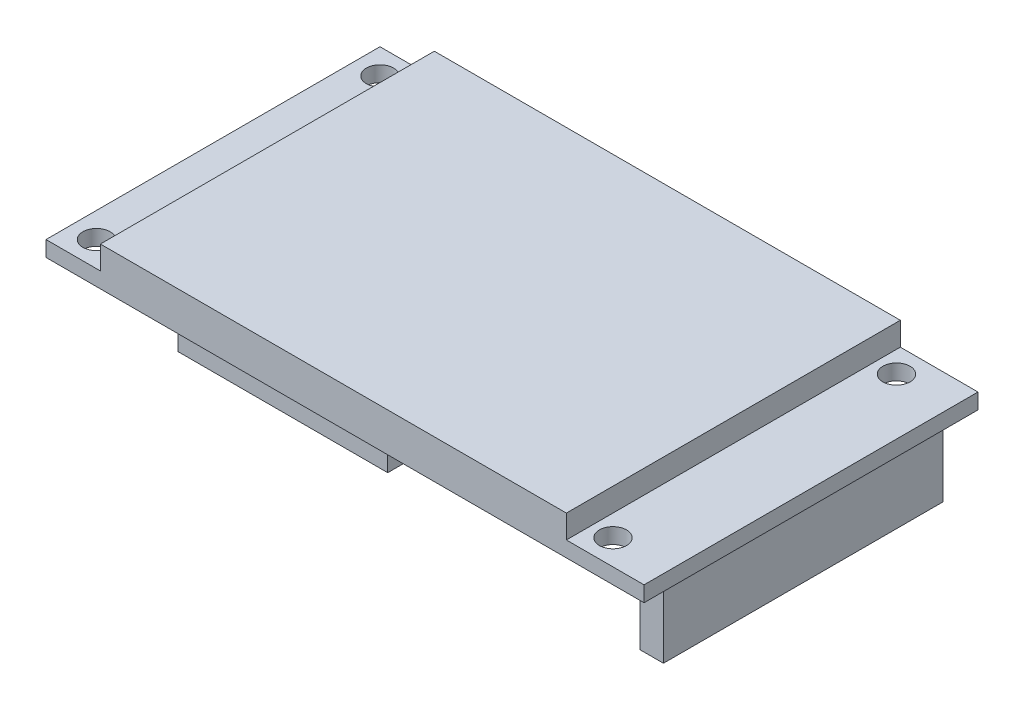
SolidWorks part; units mm, degrees
ref_plane "Front Plane" through (0, 0, 0) normal (0, 0, 1) x (1, 0, 0)
ref_plane "Top Plane" through (0, 0, 0) normal (0, 1, 0) x (1, 0, 0)
ref_plane "Right Plane" through (0, 0, 0) normal (1, 0, 0) x (0, 0, -1)
sketch "Sketch1" plane through (0, 0, 0) normal (0, 1, 0) x (1, 0, 0)
  line L1 (-38.5, 21.5) -> (38.5, 21.5)
  line L2 (-38.5, 21.5) -> (-38.5, -21.5)
  line L3 (-38.5, -21.5) -> (38.5, -21.5)
  line L4 (38.5, 21.5) -> (38.5, -21.5)
  line L5 (-38.5, 21.5) -> (38.5, -21.5) construction
  line L6 (-38.5, -21.5) -> (38.5, 21.5) construction
  line L7 (-31.5, 21.5) -> (28.5, 21.5)
  line L8 (-31.5, 21.5) -> (-31.5, -21.5)
  line L9 (-31.5, -21.5) -> (28.5, -21.5)
  line L10 (28.5, 21.5) -> (28.5, -21.5)
  line L11 (-31.5, 21.5) -> (28.5, -21.5) construction
  line L12 (-31.5, -21.5) -> (28.5, 21.5) construction
  point P0 (0, 0)
  point P6 (-1.5, 0)
  dimension "D1" = 43
  dimension "D2" = 77
  dimension "D3" = 0
  dimension "D4" = 43
  dimension "D5" = 10
  dimension "D6" = 7
  dimension "D7" = 60
extrude "Boss-Extrude1" add sketch "Sketch1" along normal blind 5 contours L10 L1 L8 L3 region at (-1.5, 0, 0)
extrude "Boss-Extrude2" add sketch "Sketch1<3>" along normal blind 2 contours L1 L10 L3 L4 | L8 L1 L2 L3 region at (-35, 0, 0) region at (33.5, 0, 0)
sketch "Sketch1<3>" plane through (0, 0, 0) normal (0, 1, 0) x (1, 0, 0) same geometry as "Sketch1"
sketch "Sketch2" plane through (0, 2, 0) normal (0, 1, 0) x (1, 0, 0)
  line L0 (28.5, 21.5) -> (38.5, 21.5) construction
  line L1 (38.5, 21.5) -> (38.5, -21.5) construction
  line L2 (28.5, -21.5) -> (38.5, -21.5) construction
  line L3 (28.5, 21.5) -> (28.5, -21.5) construction
  circle A0 centre (31.25, 18.25) radius 1.75
  circle A1 centre (31.25, -18.25) radius 1.75
  dimension "D1" = 3.5
  dimension "D4" = 3.5
  dimension "D5" = 7.25
  dimension "D6" = 3.25
  dimension "D7" = 36.5
  dimension "D2" = 3.25
  dimension "D3" = 7.25
  dimension "D8" = 2.75
extrude "Cut-Extrude1" cut sketch "Sketch2" against normal blind 2
sketch "Sketch3" plane through (0, 2, 0) normal (0, 1, 0) x (1, 0, 0)
  line L0 (-38.5, 21.5) -> (-38.5, -21.5) construction
  line L1 (-38.5, 21.5) -> (-31.5, 21.5) construction
  line L2 (-38.5, -21.5) -> (-31.5, -21.5) construction
  line L3 (-31.5, 21.5) -> (-31.5, -21.5) construction
  circle A0 centre (-35.25, 18.25) radius 1.75
  circle A1 centre (-35.25, -18.25) radius 1.75
  dimension "D1" = 3.5
  dimension "D2" = 3.5
  dimension "D4" = 3.25
  dimension "D6" = 3.25
  dimension "D7" = 36.5
  dimension "D9" = 3.75
  dimension "D3" = 3.25
  dimension "D5" = 3.25
  dimension "D8" = 3.75
extrude "Cut-Extrude2" cut sketch "Sketch3" against normal blind 2
sketch "Sketch4" plane through (0, 0, 0) normal (0, -1, 0) x (1, 0, 0)
  line L0 (-38.5, 21.5) -> (38.5, 21.5) construction
  line L1 (34.5, 18) -> (37.5, 18)
  line L2 (34.5, 18) -> (34.5, -18)
  line L3 (34.5, -18) -> (37.5, -18)
  line L4 (37.5, 18) -> (37.5, -18)
  line L5 (34.5, 18) -> (37.5, -18) construction
  line L6 (34.5, -18) -> (37.5, 18) construction
  line L7 (-38.5, -21.5) -> (38.5, -21.5) construction
  line L8 (38.5, -21.5) -> (38.5, 21.5) construction
  point P0 (36, 0)
  dimension "D1" = 36
  dimension "D2" = 3
  dimension "D3" = 3.5
  dimension "D4" = 3.5
  dimension "D5" = 1
extrude "Boss-Extrude3" add sketch "Sketch4" along normal blind 9
sketch "Sketch5" plane through (0, 0, 0) normal (0, -1, 0) x (1, 0, 0)
  line L0 (-38.5, -21.5) -> (-38.5, 21.5) construction
  line L1 (-22.5, 20.5) -> (4.5, 20.5)
  line L2 (-22.5, 20.5) -> (-22.5, 2.5)
  line L3 (-22.5, 2.5) -> (4.5, 2.5)
  line L4 (4.5, 20.5) -> (4.5, 2.5)
  line L5 (-22.5, 20.5) -> (4.5, 2.5) construction
  line L6 (-22.5, 2.5) -> (4.5, 20.5) construction
  line L7 (-38.5, 21.5) -> (38.5, 21.5) construction
  point P0 (-9, 11.5)
  dimension "D1" = 18
  dimension "D2" = 27
  dimension "D3" = 16
  dimension "D4" = 1
extrude "Boss-Extrude4" add sketch "Sketch5" along normal blind 3
